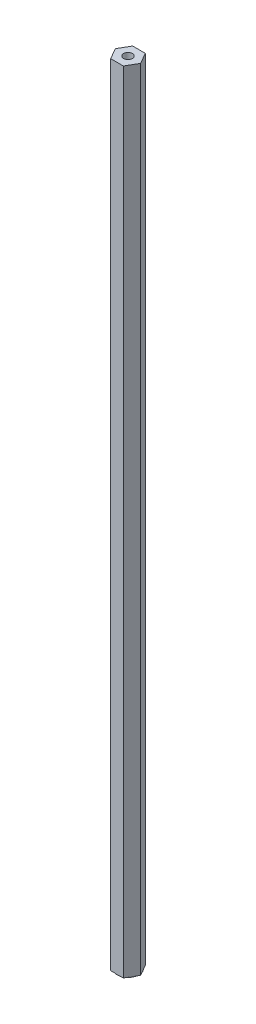
SolidWorks part; units mm, degrees
material "6063-T6"
ref_plane "Front" through (0, 0, 0) normal (0, 0, 1) x (1, 0, 0)
ref_plane "Top" through (0, 0, 0) normal (0, 1, 0) x (1, 0, 0)
ref_plane "Right" through (0, 0, 0) normal (1, 0, 0) x (0, 0, -1)
sketch "Sketch1" plane through (0, 0, 0) normal (0, 1, 0) x (1, 0, 0)
  line L1 (7.3323, 0) -> (3.6662, 6.35)
  line L2 (3.6662, 6.35) -> (-3.6662, 6.35)
  line L3 (-3.6662, 6.35) -> (-7.3323, 0)
  line L4 (-7.3323, 0) -> (-3.6662, -6.35)
  line L5 (-3.6662, -6.35) -> (3.6662, -6.35)
  line L6 (3.6662, -6.35) -> (7.3323, 0)
  circle A0 centre (0, 0) radius 6.35 construction
extrude "Boss-Extrude1" add sketch "Sketch1" along normal blind 457.2
sketch "Sketch2" plane through (0, 457.2, 0) normal (0, 1, 0) x (1, 0, 0)
  circle A0 centre (0, 0) radius 2.54
  dimension "D1" = 5.08
extrude "Cut-Extrude1" cut sketch "Sketch2" against normal blind 25.4
sketch "Sketch3" plane through (0, 0, 0) normal (0, -1, 0) x (1, 0, 0)
  circle A0 centre (0, 0) radius 6.35
extrude "Boss-Extrude2" add sketch "Sketch3" along normal blind 0.254
